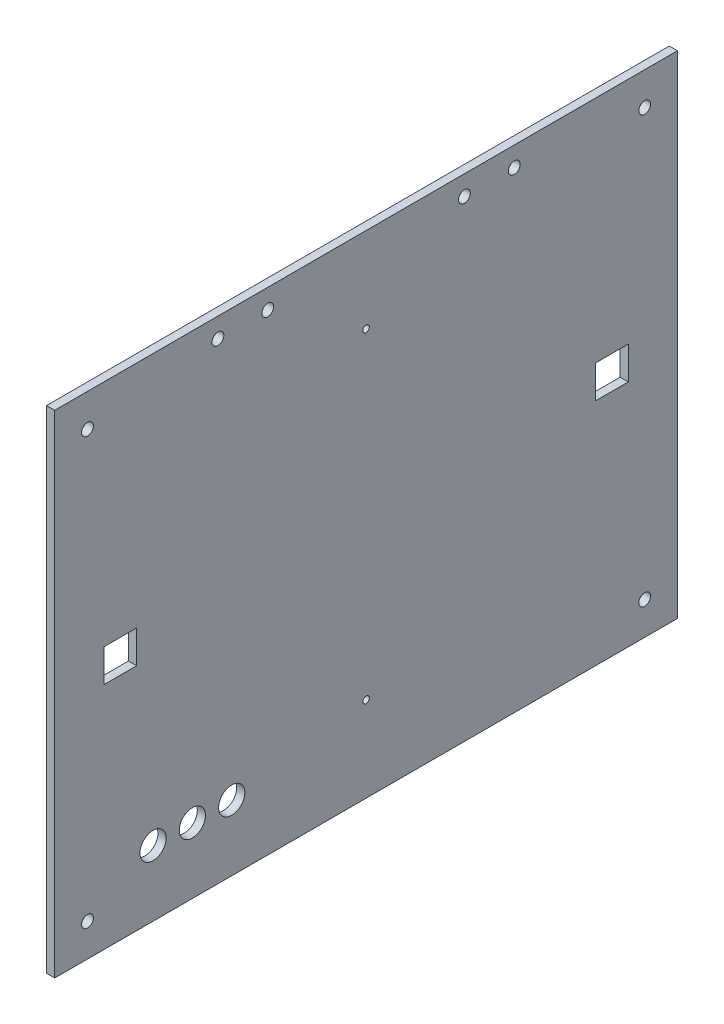
SolidWorks part; units mm, degrees
ref_plane "Front Plane" through (0, 0, 0) normal (0, 0, 1) x (1, 0, 0)
ref_plane "Top Plane" through (0, 0, 0) normal (0, 1, 0) x (1, 0, 0)
ref_plane "Right Plane" through (0, 0, 0) normal (1, 0, 0) x (0, 0, -1)
sketch "Sketch1" plane through (0, 0, 0) normal (1, 0, 0) x (0, 0, -1)
  line L1 (0, 0) -> (241.3, 0)
  line L2 (0, 0) -> (0, 190.5)
  line L3 (0, 190.5) -> (241.3, 190.5)
  line L4 (241.3, 0) -> (241.3, 190.5)
  dimension "D1" = 241.3
  dimension "D2" = 190.5
extrude "Main Body" add sketch "Sketch1" along normal blind 3.175
sketch "Sketch2" plane through (3.175, 0, 0) normal (1, 0, 0) x (0, 0, -1)
  line L2 (-1000, 95.25) -> (49000, 95.25) construction
  line L3 (0, 190.5) -> (0, 0) construction
  line L4 (120.65, -809.5) -> (120.65, 49190.5) construction
  line L5 (241.3, 190.5) -> (0, 190.5) construction
  line L6 (1228.6, 95.25) -> (-48771.4, 95.25) construction
  line L7 (241.3, 0) -> (241.3, 190.5) construction
  line L8 (0, 0) -> (241.3, 0) construction
  circle A8 centre (228.6, 12.7) radius 2.286
  circle A9 centre (228.6, 177.8) radius 2.286
  circle A10 centre (12.7, 12.7) radius 2.286
  circle A11 centre (12.7, 177.8) radius 2.286
  point P15 (0, 95.25)
  point P20 (120.65, 190.5)
  dimension "D1" = 4.572
  dimension "D3" = 12.7
  dimension "D2" = 12.7
extrude "Bolt Holes" cut sketch "Sketch2" against normal through all
sketch "Sketch3" plane through (3.175, 0, 0) normal (1, 0, 0) x (0, 0, -1)
  line L0 (241.3, 190.5) -> (0, 190.5) construction
  circle A0 centre (63.246, 182.88) radius 2.286
  circle A1 centre (82.55, 182.88) radius 2.286
  circle A2 centre (158.75, 182.88) radius 2.286
  circle A3 centre (178.054, 182.88) radius 2.286
  point P11 (120.65, 190.5)
  dimension "D1" = 4.572
  dimension "D2" = 19.304
  dimension "D4" = 7.62
  dimension "D3" = 19.304
  dimension "D5" = 38.1
  dimension "D6" = 38.1
extrude "Locking Mechanism Holes" cut sketch "Sketch3" against normal through all
sketch "Sketch4" plane through (3.175, 0, 0) normal (1, 0, 0) x (0, 0, -1)
  line L0 (0, 190.5) -> (0, 0) construction
  line L1 (19.05, 101.6) -> (31.75, 101.6)
  line L2 (19.05, 101.6) -> (19.05, 88.9)
  line L3 (19.05, 88.9) -> (31.75, 88.9)
  line L4 (31.75, 101.6) -> (31.75, 88.9)
  line L5 (209.55, 88.9) -> (222.25, 88.9)
  line L6 (209.55, 88.9) -> (209.55, 101.6)
  line L7 (209.55, 101.6) -> (222.25, 101.6)
  line L8 (222.25, 88.9) -> (222.25, 101.6)
  line L9 (241.3, 0) -> (241.3, 190.5) construction
  point P8 (19.05, 95.25)
  point P11 (0, 95.25)
  point P12 (209.55, 95.25)
  dimension "D1" = 12.7
  dimension "D2" = 12.7
  dimension "D3" = 19.05
  dimension "D4" = 19.05
extrude "LED Holes" cut sketch "Sketch4" against normal through all
sketch "Sketch5" plane through (3.175, 0, 0) normal (1, 0, 0) x (0, 0, -1)
  line L0 (241.3, 190.5) -> (0, 190.5) construction
  line L1 (120.65, 33.02) -> (120.65, 157.48) construction
  line L2 (241.3, 0) -> (241.3, 190.5) construction
  circle A0 centre (120.65, 157.48) radius 1.27
  circle A1 centre (120.65, 33.02) radius 1.27
  point P4 (120.65, 95.25)
  point P7 (120.65, 190.5)
  point P10 (241.3, 95.25)
  dimension "D2" = 2.54
  dimension "D1" = 124.46
extrude "Logo Mount Holes" cut sketch "Sketch5" against normal through all
sketch "Sketch6" plane through (3.175, 0, 0) normal (1, 0, 0) x (0, 0, -1)
  line L0 (0, 0) -> (241.3, 0) construction
  line L1 (0, 190.5) -> (0, 0) construction
  circle A0 centre (38.1, 25.4) radius 5.08
  circle A1 centre (53.34, 25.4) radius 5.08
  circle A2 centre (68.58, 25.4) radius 5.08
  point P2 (0, 0)
  point P3 (0, 0)
  dimension "D1" = 10.16
  dimension "D3" = 15.24
  dimension "D4" = 25.4
  dimension "D5" = 38.1
  dimension "D2" = 3
extrude "Panel Mount LED Hole" cut sketch "Sketch6" against normal through all
